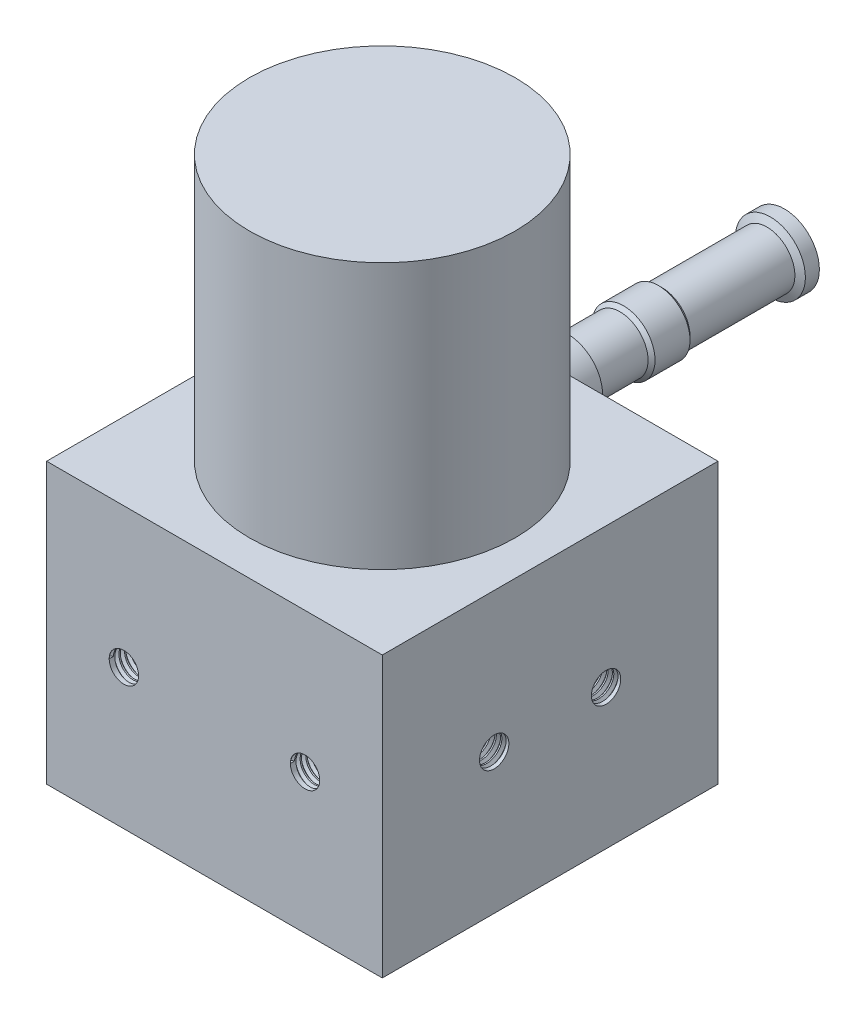
SolidWorks part; units mm, degrees
ref_plane "Frontal Plane" through (0, 0, 0) normal (0, 0, 1) x (1, 0, 0)
ref_plane "Horizontal Plane" through (0, 0, 0) normal (0, 1, 0) x (1, 0, 0)
ref_plane "Profile Plane" through (0, 0, 0) normal (1, 0, 0) x (0, 0, -1)
sketch "Sketch1" plane through (0, 0, 0) normal (0, 1, 0) x (1, 0, 0)
  line L1 (-24, -24) -> (24, -24)
  line L2 (-24, -24) -> (-24, 24)
  line L3 (-24, 24) -> (24, 24)
  line L4 (24, -24) -> (24, 24)
  line L5 (-24, -24) -> (24, 24) construction
  line L6 (-24, 24) -> (24, -24) construction
  point P0 (0, 0)
  dimension "D1" = 48
  dimension "D2" = 48
extrude "Boss-Extrude1" add sketch "Sketch1" along normal blind 40
sketch "Sketch2" plane through (0, 40, 0) normal (0, 1, 0) x (1, 0, 0)
  circle A0 centre (0, 0) radius 19
  dimension "D1" = 38
extrude "Boss-Extrude2" add sketch "Sketch2" along normal blind 38
sketch "Sketch4" plane through (0, 0, -24) normal (0, 0, -1) x (-1, 0, 0)
  line L0 (-24, 0) -> (24, 0) construction
  circle A0 centre (12.5, 25) radius 5
  dimension "D3" = 10
  dimension "D1" = 25
  dimension "D2" = 12.5
extrude "Boss-Extrude3" add sketch "Sketch4" along normal blind 46
ref_plane "Plane1" through (-12.5, 0, 0) normal (1, 0, 0) x (0, 0, -1)
sketch "Sketch5" plane through (-12.5, 0, 0) normal (1, 0, 0) x (0, 0, -1)
  line L0 (39, 30) -> (39, 29)
  line L1 (70, 30) -> (24, 30) construction
  line L6 (39, 30) -> (68, 30)
  line L7 (39, 29) -> (46.5, 29)
  line L8 (46.5, 29) -> (47, 29.5)
  line L9 (47, 29.5) -> (52, 29.5)
  line L10 (52, 29.5) -> (52.5, 29)
  line L11 (52.5, 29) -> (67.5, 29)
  line L13 (24, 20) -> (24, 30) construction
  line L14 (24, 25) -> (70, 25) construction
  line L15 (70, 20) -> (70, 30) construction
  line L16 (67.5, 29) -> (68, 30)
  line L17 (39, 25) -> (70, 25)
  line L18 (70, 25) -> (70, 27)
  line L19 (70, 27) -> (39, 27)
  line L20 (39, 27) -> (39, 25)
  dimension "D1" = 1
  dimension "D2" = 7.5
  dimension "D3" = 135
  dimension "D4" = 5
  dimension "D5" = 0.5
  dimension "D6" = 15
  dimension "D7" = 15
  dimension "D8" = 1
  dimension "D9" = 2
  dimension "D10" = 2
revolve "Cut-Revolve1" cut sketch "Sketch5" angle 360 about L14
sketch "Sketch6" plane through (0, 0, 24) normal (0, 0, 1) x (1, 0, 0)
  line L1 (-24, 0) -> (24, 0) construction
  circle A0 centre (-12.954, 20) radius 2.1
  circle A1 centre (12.954, 20) radius 2.1
  dimension "D3" = 4.2
  dimension "D2" = 20
  dimension "D4" = 25.908
  dimension "D1" = 12.954
extrude "Cut-Extrude1" cut sketch "Sketch6" against normal blind 5
sketch "Sketch8" plane through (24, 0, 0) normal (1, 0, 0) x (0, 0, -1)
  line L0 (-24, 0) -> (24, 0) construction
  circle A0 centre (8, 20) radius 2.1
  circle A1 centre (-8, 20) radius 2.1
  dimension "D1" = 4.2
  dimension "D2" = 20
  dimension "D3" = 16
  dimension "D4" = 8
extrude "Cut-Extrude2" cut sketch "Sketch8" against normal blind 5
thread "Thread1" pitch 0.8 method cut profile "Thread Profile1" start angle 0, offset 0, length 0, pitch 0.8, diameter 4.2
ref_plane "Plane2" through (24, 20, 10.1) normal (0, -1, 0) x (0, 0, 1)
sketch "Thread Profile1" plane through (24, 20, 10.1) normal (0, -1, 0) x (0, 0, 1)
  line L0 (0, 0) -> (0, 0.8) construction
  line L1 (0, 0) -> (0.433, 0.25)
  line L2 (0.433, 0.25) -> (0.433, 0.35)
  line L3 (0.433, 0.35) -> (0, 0.6)
  line L4 (0.433, 0.3) -> (0, 0.3) construction
  line L11 (0, 0) -> (0, 0.6)
  point P2 (0, 0)
  dimension "Pitch" = 0.8
  dimension "Profile_Angle" = 60
  dimension "Profile_Land" = 0.1
  dimension "Profile_Height" = 0.433
thread "Thread2" pitch 0.8 method cut profile "Thread Profile2" start angle 0, offset 0, length 0, pitch 0.8, diameter 4.2
ref_plane "Plane3" through (24, 20, -5.9) normal (0, -1, 0) x (0, 0, 1)
sketch "Thread Profile2" plane through (24, 20, -5.9) normal (0, -1, 0) x (0, 0, 1)
  line L0 (0, 0) -> (0, 0.8) construction
  line L1 (0, 0) -> (0.433, 0.25)
  line L2 (0.433, 0.25) -> (0.433, 0.35)
  line L3 (0.433, 0.35) -> (0, 0.6)
  line L4 (0.433, 0.3) -> (0, 0.3) construction
  line L11 (0, 0) -> (0, 0.6)
  point P2 (0, 0)
  dimension "Pitch" = 0.8
  dimension "Profile_Angle" = 60
  dimension "Profile_Land" = 0.1
  dimension "Profile_Height" = 0.433
thread "Thread3" pitch 0.8 method cut profile "Thread Profile3" start angle 0, offset 0, length 0, pitch 0.8, diameter 4.2
ref_plane "Plane4" through (10.854, 20, 24) normal (0, -1, 0) x (-1, 0, 0)
sketch "Thread Profile3" plane through (10.854, 20, 24) normal (0, -1, 0) x (-1, 0, 0)
  line L0 (0, 0) -> (0, 0.8) construction
  line L1 (0, 0) -> (0.433, 0.25)
  line L2 (0.433, 0.25) -> (0.433, 0.35)
  line L3 (0.433, 0.35) -> (0, 0.6)
  line L4 (0.433, 0.3) -> (0, 0.3) construction
  line L11 (0, 0) -> (0, 0.6)
  point P2 (0, 0)
  dimension "Pitch" = 0.8
  dimension "Profile_Angle" = 60
  dimension "Profile_Land" = 0.1
  dimension "Profile_Height" = 0.433
thread "Thread4" pitch 0.8 method cut profile "Thread Profile4" start angle 0, offset 0, length 0, pitch 0.8, diameter 4.2
ref_plane "Plane5" through (-15.054, 20, 24) normal (0, -1, 0) x (-1, 0, 0)
sketch "Thread Profile4" plane through (-15.054, 20, 24) normal (0, -1, 0) x (-1, 0, 0)
  line L0 (0, 0) -> (0, 0.8) construction
  line L1 (0, 0) -> (0.433, 0.25)
  line L2 (0.433, 0.25) -> (0.433, 0.35)
  line L3 (0.433, 0.35) -> (0, 0.6)
  line L4 (0.433, 0.3) -> (0, 0.3) construction
  line L11 (0, 0) -> (0, 0.6)
  point P2 (0, 0)
  dimension "Pitch" = 0.8
  dimension "Profile_Angle" = 60
  dimension "Profile_Land" = 0.1
  dimension "Profile_Height" = 0.433
equation "\"D1@Sketch6\"=\"D4@Sketch6\"/2"
